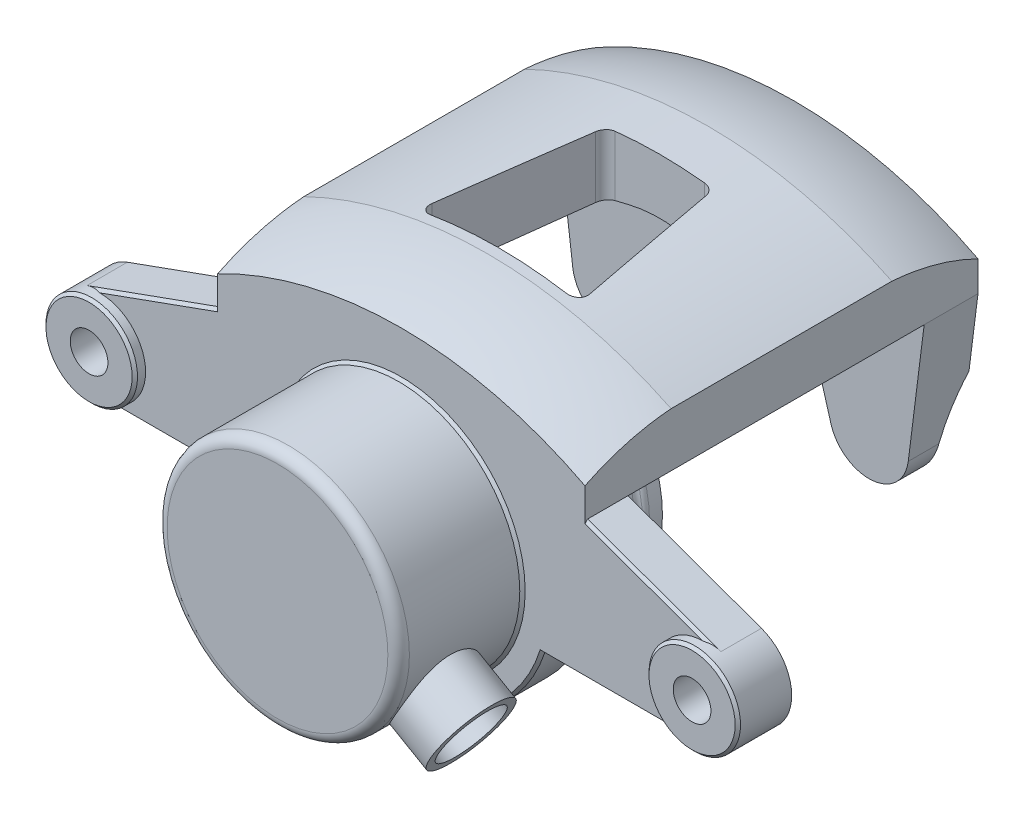
SolidWorks part; units mm, degrees
ref_plane "Płaszczyzna przednia" through (0, 0, 0) normal (0, 0, 1) x (1, 0, 0)
ref_plane "Płaszczyzna górna" through (0, 0, 0) normal (0, 1, 0) x (1, 0, 0)
ref_plane "Płaszczyzna prawa" through (0, 0, 0) normal (1, 0, 0) x (0, 0, -1)
sketch "Szkic3" plane through (0, 0, 0) normal (0, 0, 1) x (1, 0, 0)
  line L46 (-40.3579, 88.0343) -> (-42.6828, 89.5)
  line L47 (-42.6828, 89.5) -> (-44.5, 89.5)
  line L48 (-44.5, 89.5) -> (-44.5, 85.5)
  line L49 (-46.5, 83.5) -> (-48.5, 83.5)
  line L50 (-50.5, 85.5) -> (-50.5, 106.5)
  line L51 (-48.5, 108.5) -> (-46.5, 108.5)
  line L52 (-44.5, 106.5) -> (-44.5, 104.5)
  line L53 (-44.5, 104.5) -> (-43.5, 104.5)
  line L54 (-43.5, 104.5) -> (-43.5, 130)
  line L55 (-44, 130.5) -> (-50.7929, 130.5)
  line L56 (-50.7929, 130.5) -> (-57.5943, 123.6986)
  line L57 (57.5943, 123.6986) -> (50.7929, 130.5)
  line L58 (50.7929, 130.5) -> (44, 130.5)
  line L59 (43.5, 130) -> (43.5, 104.5)
  line L60 (43.5, 104.5) -> (44.5, 104.5)
  line L61 (44.5, 104.5) -> (44.5, 106.5)
  line L62 (46.5, 108.5) -> (48.5, 108.5)
  line L63 (50.5, 106.5) -> (50.5, 85.5)
  line L64 (48.5, 83.5) -> (46.5, 83.5)
  line L65 (44.5, 85.5) -> (44.5, 89.5)
  line L66 (44.5, 89.5) -> (42.6828, 89.5)
  line L67 (42.6828, 89.5) -> (40.3579, 88.0343)
  line L68 (13.6926, 80.3305) -> (-13.6926, 80.3305)
  circle A2 centre (56, 105) radius 3.5
  circle A5 centre (43, 72.2969) radius 4
  circle A6 centre (-43, 72.2969) radius 4
  circle A7 centre (-56, 105) radius 3.5
  arc A46 (-46.5, 83.5) -> (-44.5, 85.5) centre (-46.5, 85.5) ccw
  arc A47 (-50.5, 85.5) -> (-48.5, 83.5) centre (-48.5, 85.5) ccw
  arc A48 (-48.5, 108.5) -> (-50.5, 106.5) centre (-48.5, 106.5) ccw
  arc A49 (-44.5, 106.5) -> (-46.5, 108.5) centre (-46.5, 106.5) ccw
  arc A50 (-43.5, 130) -> (-44, 130.5) centre (-44, 130) ccw
  arc A51 (-57.5943, 123.6986) -> (-57.6155, 81.3412) centre (-18, 102.5) ccw
  arc A52 (-57.6155, 81.3412) -> (-50.0301, 76.524) centre (0, 163.6859) ccw
  arc A53 (-50.0301, 76.524) -> (-35.2615, 69.5752) centre (-43, 72.2969) ccw
  arc A54 (-35.2615, 69.5752) -> (35.2615, 69.5752) centre (0, 163.6859) ccw
  arc A55 (35.2615, 69.5752) -> (50.0301, 76.524) centre (43, 72.2969) ccw
  arc A56 (50.0301, 76.524) -> (57.6155, 81.3412) centre (0, 163.6859) ccw
  arc A57 (57.6155, 81.3412) -> (57.5943, 123.6986) centre (18, 102.5) ccw
  arc A58 (44, 130.5) -> (43.5, 130) centre (44, 130) ccw
  arc A59 (46.5, 108.5) -> (44.5, 106.5) centre (46.5, 106.5) ccw
  arc A60 (50.5, 106.5) -> (48.5, 108.5) centre (48.5, 106.5) ccw
  arc A61 (48.5, 83.5) -> (50.5, 85.5) centre (48.5, 85.5) ccw
  arc A62 (44.5, 85.5) -> (46.5, 83.5) centre (46.5, 85.5) ccw
  arc A63 (13.6926, 80.3305) -> (40.3579, 88.0343) centre (13.6926, 130.3305) ccw
  arc A64 (-40.3579, 88.0343) -> (-13.6926, 80.3305) centre (-13.6926, 130.3305) ccw
sketch "Szkic4" plane through (0, 0, 0) normal (0, 0, 1) x (1, 0, 0)
  line L0 (-56, 96.5) -> (-26.1534, 96.5)
  line L1 (56, 96.5) -> (26.1534, 96.5)
  line L2 (9.3304, 130.8688) -> (58.8839, 112.9958)
  line L3 (-9.3304, 130.8688) -> (-58.8839, 112.9958)
  circle A0 centre (-56, 105) radius 3.5
  circle A1 centre (56, 105) radius 3.5
  circle A2 centre (0, 105) radius 17.5
  circle A3 centre (56, 105) radius 8.5
  circle A4 centre (-56, 105) radius 8.5
  circle A5 centre (0, 105) radius 22.5
  circle A6 centre (0, 105) radius 27.5
  dimension "D1" = 35
  dimension "D2" = 5
  dimension "D3" = 5
  dimension "D4" = 10
extrude "Dodanie-wyciągnięcie1" add sketch "Szkic4" along normal blind 8 contours A6 L3 A4 L0 | A4 A0 | A6 A5 | A5 A2 | A6 L1 A3 L2 | A3 A1 region at (-36.4854, 110.0723, 0) region at (-64.1362, 103.5776, 0) region at (-24.0011, 116.7482, 0) region at (36.4854, 110.0723, 0) region at (47.8638, 106.4224, 0) region at (-21.8636, 105, 0)
extrude "Dodanie-wyciągnięcie2" add sketch "Szkic4<3>" along normal blind 2 from surface contours A4 A0 | A3 A1 region at (-64.1362, 103.5776, 0) region at (47.8638, 106.4224, 0) starting at face at (0, 106.7421, 8)
sketch "Szkic4<3>" plane through (0, 0, 0) normal (0, 0, 1) x (1, 0, 0) same geometry as "Szkic4"
ref_axis "Oś1" through (0, 105, 8) along (0, 0, -1)
sketch "Szkic6" plane through (0, 0, 0) normal (1, 0, 0) x (0, 0, -1)
  line L0 (0, 104.9333) -> (0, 87.5)
  line L1 (0, 87.5) -> (0, 122.5)
  line L2 (0, 122.5) -> (15, 122.5)
  line L3 (17, 123) -> (17, 128.5)
  line L4 (17, 128.5) -> (14.618, 128.5)
  line L5 (13.7236, 127.9472) -> (13.7764, 128.0528)
  line L6 (12.882, 127.5) -> (5.118, 127.5)
  line L7 (4.2236, 128.0528) -> (4.2764, 127.9472)
  line L8 (3.382, 128.5) -> (1, 128.5)
  line L9 (0, 130) -> (0, 104.5) construction
  line L10 (0, 128.5) -> (0, 122.5)
  line L11 (0, 129.5) -> (0, 130)
  line L12 (0, 129.5) -> (0, 122.5)
  line L13 (17, 123) -> (17, 128.5)
  line L16 (16, 123) -> (16, 123.5)
  line L17 (16, 123.5) -> (15, 123.5)
  line L18 (15, 123.5) -> (15, 122.5)
  line L20 (15, 122.5) -> (0, 122.5)
  line L21 (16, 123) -> (17, 123)
  arc A0 (14.618, 128.5) -> (13.7236, 127.9472) centre (14.618, 127.5) ccw
  arc A1 (13.7764, 128.0528) -> (12.882, 127.5) centre (12.882, 128.5) cw
  arc A2 (4.2764, 127.9472) -> (3.382, 128.5) centre (3.382, 127.5) ccw
  arc A3 (5.118, 127.5) -> (4.2236, 128.0528) centre (5.118, 128.5) cw
  arc A4 (1, 128.5) -> (0, 129.5) centre (1, 129.5) cw
  point P8 (2.191, 128.5)
  point P19 (14, 128.5)
  point P22 (13.5, 127.5)
  point P27 (4.5, 127.5)
  dimension "D7" = 1
  dimension "D2" = 3
  dimension "D4" = 5
  dimension "D5" = 6
  dimension "D6" = 9
  dimension "D9" = 1
  dimension "D10" = 1
revolve "Obrót1" add sketch "Szkic6" angle 360 about axis through (0, 105, 8) along (0, 0, -1) region at (0, 125.2877, -8.3079)
extrude "Dodanie-wyciągnięcie3" add sketch "Szkic4<5>" along normal blind 20 from surface contours A5 A2 region at (-21.8636, 105, 0) starting at face at (17.5, 105, 8)
sketch "Szkic4<5>" plane through (0, 0, 0) normal (0, 0, 1) x (1, 0, 0) same geometry as "Szkic4"
sketch "Szkic8" plane through (0, 0, 0) normal (0, 0, -1) x (-1, 0, 0)
  line L1 (-9.3304, 130.8688) -> (-58.8839, 112.9958) construction
  line L2 (9.3304, 130.8688) -> (58.8839, 112.9958) construction
  line L3 (-34.1071, 121.9323) -> (-34.1071, 131.9323)
  line L4 (34.1071, 121.9323) -> (34.1071, 131.9323)
  line L5 (34.1071, 121.9323) -> (58.8839, 112.9958)
  line L6 (-34.1071, 121.9323) -> (-58.8839, 112.9958)
  line L7 (34.1071, 121.9323) -> (5.7793, 128.8086)
  line L8 (-34.1071, 121.9323) -> (-5.7793, 128.8086)
  arc A1 (-34.1071, 131.9323) -> (34.1071, 131.9323) centre (0, 61.9323) cw
  circle A3 centre (0, 105) radius 24.5 construction
  arc A5 (5.7793, 128.8086) -> (-5.7793, 128.8086) centre (0, 105) ccw
  circle M5 centre (0, 105) radius 24.5
  line M8 (58.8839, 112.9958) -> (9.3304, 130.8688)
  arc M9 (9.3304, 130.8688) -> (-9.3304, 130.8688) centre (0, 105) ccw
  line M10 (-9.3304, 130.8688) -> (-58.8839, 112.9958)
  dimension "D1" = 10
  dimension "D3" = 10
extrude "Dodanie-wyciągnięcie4" add sketch "Szkic8" against normal up to surface (8 mm away) contours A1 L3 L4 M10 M9 M8 up to face at (0, 107.474, 8)
extrude "Dodanie-wyciągnięcie5" add sketch "Szkic8<3>" along normal blind 55 contours L6 | A1 L3 L4 M10 M9 M8 | L8 L7 M10 M5 M8 M9 region at (21.4845, 125.7512, 0) region at (33.402, 126.9323, 0)
sketch "Szkic8<3>" plane through (0, 0, 0) normal (0, 0, -1) x (-1, 0, 0) same geometry as "Szkic8"
sketch "Szkic9" plane through (0, 0, -55) normal (0, 0, -1) x (-1, 0, 0)
  line L0 (-34.1071, 121.9323) -> (-31.1543, 98.4757)
  line L1 (-16.7965, 97.3481) -> (-12.5622, 111.9642)
  line L2 (0, 34.2647) -> (0, -34.2647) construction
  line L3 (34.1071, 121.9323) -> (31.1543, 98.4757)
  line L4 (-34.1071, 131.9323) -> (-34.1071, 121.9323)
  line L5 (-34.1071, 121.9323) -> (-5.7793, 128.8086)
  line L6 (-34.1071, 121.9323) -> (-5.7793, 128.8086)
  line L7 (34.1071, 121.9323) -> (34.1071, 131.9323)
  line L8 (-34.1071, 131.9323) -> (-34.1071, 121.9323)
  line L11 (34.1071, 121.9323) -> (34.1071, 131.9323)
  line L12 (16.7965, 97.3481) -> (12.5622, 111.9642)
  line L17 (5.7793, 128.8086) -> (34.1071, 121.9323)
  line L18 (5.7793, 128.8086) -> (34.1071, 121.9323)
  arc A0 (-31.1543, 98.4757) -> (-16.7965, 97.3481) centre (-23.859, 99.3941) ccw
  arc A1 (31.1543, 98.4757) -> (16.7965, 97.3481) centre (23.859, 99.3941) cw
  arc A2 (5.7793, 128.8086) -> (-5.7793, 128.8086) centre (0, 105) ccw
  arc A3 (34.1071, 131.9323) -> (-34.1071, 131.9323) centre (0, 61.9323) ccw
  arc A5 (34.1071, 131.9323) -> (-34.1071, 131.9323) centre (0, 61.9323) ccw
  arc A6 (-12.5622, 111.9642) -> (12.5622, 111.9642) centre (0, 108.3248) cw
  arc A9 (5.7793, 128.8086) -> (-5.7793, 128.8086) centre (0, 105) ccw
  point P19 (0, 155.3258)
  line M9 (-34.1071, 131.9323) -> (-34.1071, 121.9323)
  line M13 (34.1071, 121.9323) -> (34.1071, 131.9323)
  arc M14 (34.1071, 131.9323) -> (-34.1071, 131.9323) centre (0, 61.9323) ccw
  arc M32 (-5.7793, 128.8086) -> (5.7793, 128.8086) centre (0, 105) cw
  line M40 (-34.1071, 121.9323) -> (-5.7793, 128.8086)
  line M41 (5.7793, 128.8086) -> (34.1071, 121.9323)
  dimension "D1" = 0
extrude "Dodanie-wyciągnięcie6" add sketch "Szkic9" along normal blind 10 contours L1 A6 L12 A1 L3 L0 A0 M41 M32 M40 | M14 M9 M40 M32 M41 M13 region at (19.7596, 124.6142, -55) region at (0, 131.6317, -55)
sketch "Szkic10" plane through (0, 0, 0) normal (1, 0, 0) x (0, 0, -1)
  line L0 (65, 92.0413) -> (65, 98.4757) construction
  line L1 (65, 121.9323) -> (65, 98.4757) construction
  line L2 (65, 131.9323) -> (65, 121.9323) construction
  line L3 (65, 131.9323) -> (65, 139.7995) construction
  line L4 (65, 139.7995) -> (-8, 139.7995) construction
  line L6 (-8, 121.9323) -> (-8, 131.9323) construction
  line L7 (-8, 121.9323) -> (0, 121.9323) construction
  line L8 (55, 121.9323) -> (0, 121.9323) construction
  line L9 (55, 92.0413) -> (65, 92.0413) construction
  line L10 (55, 98.4757) -> (55, 92.0413) construction
  line L11 (55, 121.9323) -> (55, 98.4757) construction
  line L12 (65, 92.0413) -> (65, 98.4757)
  line L13 (65, 121.9323) -> (65, 98.4757)
  line L14 (65, 131.9323) -> (65, 121.9323)
  line L15 (65, 131.9323) -> (65, 135.8659)
  line L18 (-8, 121.9323) -> (-8, 131.9323)
  line L19 (-8, 121.9323) -> (0, 121.9323)
  line L20 (55, 121.9323) -> (0, 121.9323)
  line L21 (55, 92.0413) -> (65, 92.0413)
  line L22 (55, 98.4757) -> (55, 92.0413)
  line L23 (55, 121.9323) -> (55, 98.4757)
  line L26 (49, 139.7995) -> (70.449, 156.548)
  line L27 (8, 139.7995) -> (-11.4125, 146.1959)
  line L28 (-11.4125, 146.1959) -> (-8, 135.8659)
  line L29 (70.449, 156.548) -> (65, 135.8659)
  arc A0 (60, 92.0413) -> (65, 108.6244) centre (90, 92.0413) cw
  arc A1 (-8, 135.8659) -> (8, 139.7995) centre (11.2578, 92.0413) cw
  arc A2 (65, 135.8659) -> (49, 139.7995) centre (45.7422, 92.0413) ccw
  dimension "D3" = 16
  dimension "D1" = 25
  dimension "D2" = 16
  dimension "D4" = 3.9336
extrude "Wytnij-wyciągnięcie1" cut sketch "Szkic10" against normal mid plane 100 contours A0 L21 L12 L13 region at (0, 98.3354, -62.985)
sketch "Szkic12" plane through (0, 0, 8) normal (0, 0, 1) x (1, 0, 0)
  arc A0 (34.1071, 131.9323) -> (-34.1071, 131.9323) centre (0, 61.9323) ccw construction
  arc A1 (34.1071, 131.9323) -> (-34.1071, 131.9323) centre (0, 61.9323) ccw
ref_axis "Oś2" through (0, 61.9323, 8) along (0, 0, -1)
revolve "Wycięcie-obrót2" cut sketch "Szkic10<13>" angle 80 mid plane about axis through (0, 61.9323, 8) along (0, 0, -1) region at (0, 144.3494, -61.6891) region at (0, 140.8624, 4.1643)
sketch "Szkic10<13>" plane through (0, 0, 0) normal (1, 0, 0) x (0, 0, -1) same geometry as "Szkic10"
ref_plane "Płaszczyzna1" through (0, 121.9323, 0) normal (0, 1, 0) x (1, 0, 0)
sketch "Szkic13" plane through (0, 121.9323, 0) normal (0, 1, 0) x (1, 0, 0)
  line L0 (-15, 10) -> (-10, 40)
  line L1 (-10, 40) -> (10, 40)
  line L2 (0, -8) -> (0, 65) construction
  line L3 (-15, 10) -> (15, 10)
  line L4 (-34.1071, -8) -> (34.1071, -8) construction
  line L5 (0, -34.2647) -> (0, 34.2647) construction
  line L6 (15, 10) -> (10, 40)
  point P11 (0, 10)
  point P12 (0, 40)
  dimension "D1" = 15
  dimension "D2" = 10
  dimension "D3" = 30
  dimension "D4" = 18
ref_plane "Płaszczyzna2" through (0, 151.9323, 0) normal (0, 1, 0) x (1, 0, 0)
sketch "Szkic15" plane through (0, 151.9323, 0) normal (0, 1, 0) x (1, 0, 0)
  line L0 (-15, 10) -> (15, 10) construction
  line L1 (15, 10) -> (10, 40) construction
  line L2 (-10, 40) -> (10, 40) construction
  line L3 (-15, 10) -> (-10, 40) construction
  line L4 (-12.6391, 10) -> (12.6391, 10)
  line L5 (14.6119, 12.3288) -> (10.2785, 38.3288)
  line L6 (-8.3057, 40) -> (8.3057, 40)
  line L7 (-14.6119, 12.3288) -> (-10.2785, 38.3288)
  arc A0 (-12.6391, 10) -> (-14.6119, 12.3288) centre (-12.6391, 12) cw
  arc A1 (12.6391, 10) -> (14.6119, 12.3288) centre (12.6391, 12) ccw
  arc A2 (10.2785, 38.3288) -> (8.3057, 40) centre (8.3057, 38) ccw
  arc A3 (-8.3057, 40) -> (-10.2785, 38.3288) centre (-8.3057, 38) ccw
  dimension "D1" = 2
extrude "Wytnij-wyciągnięcie7" cut sketch "Szkic15" against normal up to surface (25.9441 mm away) up to face at (0, 129.1543, -27.5)
sketch "Szkic16" plane through (0, 0, 28) normal (0, 0, 1) x (1, 0, 0)
  circle A0 centre (0, 105) radius 22.5
extrude "Dodanie-wyciągnięcie7" add sketch "Szkic16" along normal blind 3
sketch "Szkic19" plane through (0, 0, 28) normal (0, 0, -1) x (-1, 0, 0)
  circle A1 centre (0, 105) radius 17.5
  circle A2 centre (0, 105) radius 17.5
  dimension "D1" = 0
fillet "Zaokrąglenie1" radius 2 1 edges at (22.5, 105, 31)
chamfer "Sfazowanie1" distance 0.5 angle 45 6 edges at (22.5, 105, 8) (41.0767, 96.5, 8) (0, 77.5, 8) (-41.0767, 96.5, 8) (46.4955, 117.4641, 8) (-46.4955, 117.4641, 8)
chamfer "Sfazowanie2" distance 0.5 angle 45 2 edges at (-47.5, 105, 10) (64.5, 105, 10)
ref_plane "Płaszczyzna3" through (-45.4663, 26.25, 0) normal (-0.866, 0.5, 0) x (0, 0, -1)
sketch "Szkic22" plane through (-45.4663, 26.25, 0) normal (-0.866, 0.5, 0) x (0, 0, -1)
  line L0 (-8, -90.9327) -> (0, -90.9327) construction
  line L1 (-31, -70.4327) -> (-31, -111.4327) construction
  circle A0 centre (-21, -90.9327) radius 7.5
  dimension "D2" = 15
  dimension "D1" = 10
extrude "Dodanie-wyciągnięcie9" add sketch "Szkic22" along normal up to surface (8.7868 mm away) from offset 30 up to face at (22.5, 105, 8.5) offset against normal yes
sketch "Szkic23" plane through (-19.4856, 11.25, 0) normal (0.866, -0.5, 0) x (0, 0, 1)
  circle A0 centre (21, -90.9327) radius 6
  dimension "D1" = 12
extrude "Wytnij-wyciągnięcie9" cut sketch "Szkic23" against normal up to surface (13.5607 mm away) up to face at (17.5, 105, -15)
